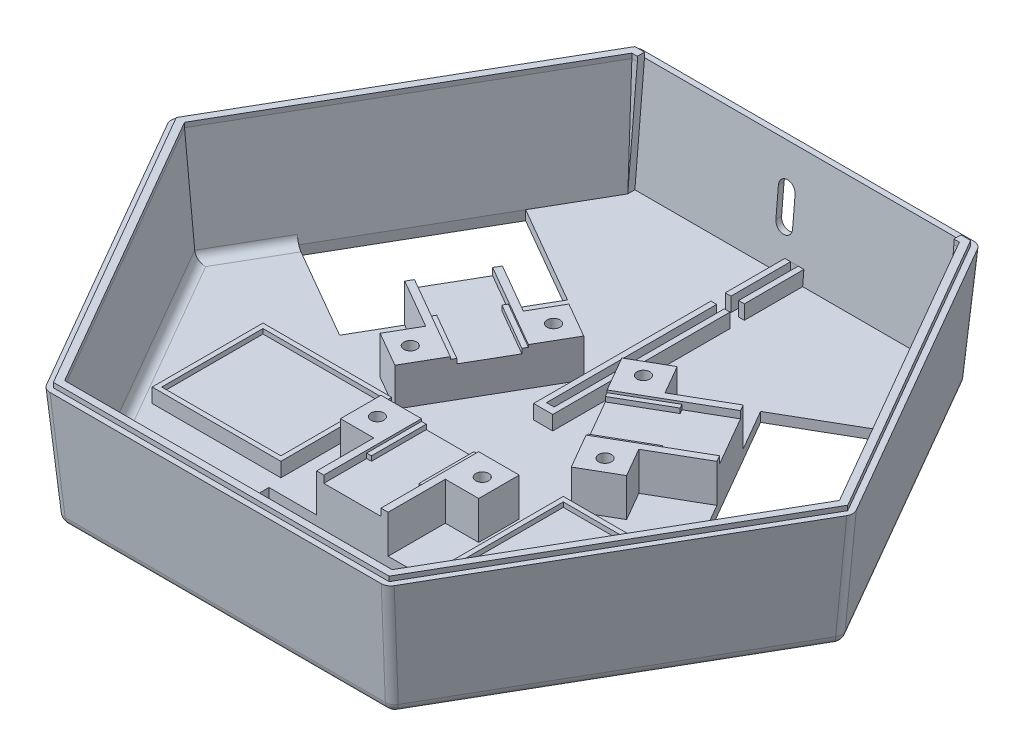
SolidWorks part; units mm, degrees
ref_plane "Front Plane" through (0, 0, 0) normal (0, 0, 1) x (1, 0, 0)
ref_plane "Top Plane" through (0, 0, 0) normal (0, 1, 0) x (1, 0, 0)
ref_plane "Right Plane" through (0, 0, 0) normal (1, 0, 0) x (0, 0, -1)
sketch "Sketch1" plane through (0, 0, 0) normal (0, 1, 0) x (1, 0, 0)
  line L1 (69.282, 0) -> (34.641, 60)
  line L2 (34.641, 60) -> (-34.641, 60)
  line L3 (-34.641, 60) -> (-69.282, 0)
  line L4 (-69.282, 0) -> (-34.641, -60)
  line L5 (-34.641, -60) -> (34.641, -60)
  line L6 (34.641, -60) -> (69.282, 0)
  circle A0 centre (0, 0) radius 60 construction
extrude "Boss-Extrude1" add sketch "Sketch1" along normal blind 25 draft 5 draft outward yes
sketch "Sketch2" plane through (0, 25, 0) normal (0, 1, 0) x (1, 0, 0)
  line L1 (68.7047, 0) -> (34.3523, 59.5)
  line L2 (34.3523, 59.5) -> (-34.3523, 59.5)
  line L3 (-34.3523, 59.5) -> (-68.7047, 0)
  line L4 (-68.7047, 0) -> (-34.3523, -59.5)
  line L5 (-34.3523, -59.5) -> (34.3523, -59.5)
  line L6 (34.3523, -59.5) -> (68.7047, 0)
  circle A0 centre (0, 0) radius 59.5 construction
extrude "Cut-Extrude1" cut sketch "Sketch2" against normal blind 23 draft 5
sketch "Sketch4" plane through (0, 2, 0) normal (0, 1, 0) x (1, 0, 0)
  line L0 (-33.1906, -57.4878) -> (33.1906, -57.4878) construction
  line L1 (-17.5, -57.4878) -> (17.5, -57.4878)
  line L2 (-17.5, -57.4878) -> (-17.5, -33.4878)
  line L3 (-17.5, -33.4878) -> (17.5, -33.4878)
  line L4 (17.5, -57.4878) -> (17.5, -33.4878)
  line L5 (-41.0359, 43.8993) -> (-20.2513, 31.8993)
  line L6 (-41.0359, 43.8993) -> (-58.5359, 13.5884)
  line L7 (-58.5359, 13.5884) -> (-37.7513, 1.5884)
  line L8 (-20.2513, 31.8993) -> (-37.7513, 1.5884)
  line L9 (58.5359, 13.5884) -> (37.7513, 1.5884)
  line L10 (58.5359, 13.5884) -> (41.0359, 43.8993)
  line L11 (41.0359, 43.8993) -> (20.2513, 31.8993)
  line L12 (37.7513, 1.5884) -> (20.2513, 31.8993)
  point P6 (0, -57.4878)
  point P7 (0, -57.4878)
  point P19 (0, 0)
  dimension "D1" = 24
  dimension "D2" = 35
  dimension "D3" = 0
  dimension "D4" = 0
  dimension "D5" = 3
extrude "Cut-Extrude3" cut sketch "Sketch4" against normal blind 3
ref_plane "Plane1" through (0, 0, -50) normal (0, 0, 1) x (1, 0, 0)
sketch "Sketch20" plane through (0, 0, -50) normal (0, 0, 1) x (1, 0, 0)
  line L0 (-2.625, 16.65) -> (-2.625, 10.65) construction
  line L1 (-0.875, 16.65) -> (-0.875, 10.65)
  line L2 (-4.375, 16.65) -> (-4.375, 10.65)
  line L3 (-17.5, 2) -> (17.5, 2) construction
  arc A0 (-0.875, 16.65) -> (-4.375, 16.65) centre (-2.625, 16.65) ccw
  arc A1 (-4.375, 10.65) -> (-0.875, 10.65) centre (-2.625, 10.65) ccw
  point P2 (-2.625, 13.65)
  point P7 (-2.625, 8.9)
  point P8 (-2.625, 18.4)
  point P9 (-4.375, 13.65)
  point P10 (-0.875, 13.65)
  dimension "D1" = 9.5
  dimension "D2" = 3.5
  dimension "D3" = 6.9
extrude "Cut-Extrude12" cut sketch "Sketch20" against normal blind 17
sketch "Sketch21" plane through (0, 2, 0) normal (0, 1, 0) x (1, 0, 0)
  line L1 (-45, -7.2378) -> (-18, -7.2378)
  line L2 (-45, -7.2378) -> (-45, -30.4878)
  line L3 (-45, -30.4878) -> (-18, -30.4878)
  line L4 (-18, -7.2378) -> (-18, -30.4878)
  line L5 (17.5, -33.4878) -> (-17.5, -33.4878) construction
  line L7 (18, -7.2378) -> (45, -7.2378)
  line L8 (18, -7.2378) -> (18, -30.4878)
  line L9 (18, -30.4878) -> (45, -30.4878)
  line L10 (45, -7.2378) -> (45, -30.4878)
  line L11 (17.5, -33.4878) -> (-17.5, -33.4878) construction
  dimension "D1" = 27
  dimension "D2" = 23.25
  dimension "D4" = 3
  dimension "D6" = 27
  dimension "D7" = 3
extrude "Boss-Extrude7" add sketch "Sketch21" along normal blind 3
sketch "Sketch22" plane through (0, 5, 0) normal (0, 1, 0) x (1, 0, 0)
  line L0 (-18, -30.4878) -> (-18, -7.2378) construction
  line L1 (-44, -8.2378) -> (-19, -8.2378)
  line L2 (-44, -8.2378) -> (-44, -29.4878)
  line L3 (-44, -29.4878) -> (-19, -29.4878)
  line L4 (-19, -8.2378) -> (-19, -29.4878)
  line L5 (19, -8.2378) -> (44, -8.2378)
  line L6 (19, -8.2378) -> (19, -29.4878)
  line L7 (19, -29.4878) -> (44, -29.4878)
  line L8 (44, -8.2378) -> (44, -29.4878)
  line L9 (-45, -7.2378) -> (-45, -30.4878) construction
  line L10 (-45, -30.4878) -> (-18, -30.4878) construction
  line L11 (-18, -7.2378) -> (-45, -7.2378) construction
  line L12 (45, -7.2378) -> (18, -7.2378) construction
  line L13 (18, -7.2378) -> (18, -30.4878) construction
  dimension "D1" = 1
  dimension "D2" = 1
  dimension "D3" = 1
  dimension "D4" = 1
  dimension "D5" = 25
  dimension "D6" = 21.25
  dimension "D7" = 1
  dimension "D8" = 1
extrude "Cut-Extrude13" cut sketch "Sketch22" against normal blind 1
fillet "Fillet2" radius 2 6 edges at (25.3453, 2, 57.4878) (-25.3453, 2, 57.4878) (-62.4585, 2, -6.7942) (-49.7859, 2, 28.7439) (49.7859, 2, 28.7439) (62.4585, 2, -6.7942)
fillet "Fillet3" radius 2 12 edges at (-51.9615, 0, -30) (-35.2724, 12.5, -61.0936) (0, 0, -60) (35.2724, 12.5, -61.0936) (51.9615, 0, -30) (70.5448, 12.5, 0) (51.9615, 0, 30) (35.2724, 12.5, 61.0936) (0, 0, 60) (-51.9615, 0, 30) (-35.2724, 12.5, 61.0936) (-70.5448, 12.5, 0)
sketch "Sketch24" plane through (0, 25, 0) normal (0, 1, 0) x (1, 0, 0)
  line L1 (70.4367, 0) -> (35.2184, 61)
  line L2 (35.2184, 61) -> (-35.2184, 61)
  line L3 (-35.2184, 61) -> (-70.4367, 0)
  line L4 (-70.4367, 0) -> (-35.2184, -61)
  line L5 (-35.2184, -61) -> (35.2184, -61)
  line L6 (35.2184, -61) -> (70.4367, 0)
  circle A0 centre (0, 0) radius 61 construction
extrude "Boss-Extrude8" add sketch "Sketch24" along normal blind 1
sketch "Sketch25" plane through (0, 26, 0) normal (0, 1, 0) x (1, 0, 0)
  line L1 (68.7047, 0) -> (34.3523, 59.5)
  line L2 (34.3523, 59.5) -> (-34.3523, 59.5)
  line L3 (-34.3523, 59.5) -> (-68.7047, 0)
  line L4 (-68.7047, 0) -> (-34.3523, -59.5)
  line L5 (-34.3523, -59.5) -> (34.3523, -59.5)
  line L6 (34.3523, -59.5) -> (68.7047, 0)
  circle A0 centre (0, 0) radius 59.5 construction
extrude "Cut-Extrude16" cut sketch "Sketch25" against normal blind 1
sketch "Sketch26" plane through (0, 2, 0) normal (0, 1, 0) x (1, 0, 0)
  line L0 (-25.2513, 23.2391) -> (-14.8589, 17.2391)
  line L1 (-37.7513, 1.5884) -> (-20.2513, 31.8993) construction
  line L2 (-14.8589, 17.2391) -> (-11.3589, 23.3012)
  line L3 (-11.3589, 23.3012) -> (-3.9977, 19.0512)
  line L4 (-3.9977, 19.0512) -> (-18.4977, -6.0635)
  line L5 (-18.4977, -6.0635) -> (-25.8589, -1.8135)
  line L6 (-25.8589, -1.8135) -> (-22.3589, 4.2487)
  line L7 (-22.3589, 4.2487) -> (-32.7513, 10.2487)
  line L8 (-32.7513, 10.2487) -> (-25.2513, 23.2391)
  line L9 (25.2513, 23.2391) -> (32.7513, 10.2487)
  line L10 (32.7513, 10.2487) -> (22.3589, 4.2487)
  line L11 (22.3589, 4.2487) -> (25.8589, -1.8135)
  line L12 (25.8589, -1.8135) -> (18.4977, -6.0635)
  line L13 (18.4977, -6.0635) -> (3.9977, 19.0512)
  line L14 (3.9977, 19.0512) -> (11.3589, 23.3012)
  line L15 (11.3589, 23.3012) -> (14.8589, 17.2391)
  line L16 (14.8589, 17.2391) -> (25.2513, 23.2391)
  line L17 (7.5, -33.4878) -> (-7.5, -33.4878)
  line L18 (-7.5, -33.4878) -> (-7.5, -21.4878)
  line L19 (-7.5, -21.4878) -> (-14.5, -21.4878)
  line L20 (-14.5, -21.4878) -> (-14.5, -12.9878)
  line L21 (-14.5, -12.9878) -> (14.5, -12.9878)
  line L22 (14.5, -12.9878) -> (14.5, -21.4878)
  line L23 (14.5, -21.4878) -> (7.5, -21.4878)
  line L24 (7.5, -21.4878) -> (7.5, -33.4878)
  point P4 (-29.0013, 16.7439)
  point P11 (-29.0013, 16.7439)
  point P31 (0, 0)
  dimension "D1" = 15
  dimension "D2" = 12
  dimension "D3" = 12
  dimension "D4" = 7
  dimension "D5" = 7
  dimension "D6" = 8.5
  dimension "D7" = 8.5
  dimension "D8" = 0
  dimension "D9" = 3
extrude "Boss-Extrude9" add sketch "Sketch26" along normal blind 8 contours L8 L0 L2 L3 L4 L5 L6 L7 | L17 L18 L19 L20 L21 L22 L23 L24 | L9 L10 L11 L12 L13 L14 L15 L16
sketch "Sketch37" plane through (0, 0, 0) normal (1, 0, 0) x (0, 0, -1)
  line L0 (57.4878, 2) -> (58.9776, 2)
  line L1 (58.9776, 2) -> (61, 25)
  line L2 (61, 25) -> (61.3953, 29.4952)
  line L3 (61.3953, 29.4952) -> (58.5935, 29.7415)
  line L4 (58.5935, 29.7415) -> (55.5776, 2)
  line L5 (43.8993, 2) -> (57.4878, 2) construction
  line L6 (55.5776, 2) -> (57.4878, 2)
extrude "Cut-Extrude21" cut sketch "Sketch37" against normal blind 33.2 and the other way blind 33.2
sketch "Sketch38" plane through (0, 0, 0) normal (1, 0, 0) x (0, 0, -1)
  line L0 (58.9776, 2) -> (59.2414, 5)
  line L1 (58.9776, 2) -> (61, 25) construction
  line L2 (59.2414, 5) -> (46.7414, 5)
  line L3 (46.7414, 5) -> (46.7414, 2)
  line L4 (43.8993, 2) -> (57.4714, 2) construction
  line L5 (46.7414, 2) -> (58.9776, 2)
  line L6 (43.7414, 2) -> (43.7414, 5)
  line L7 (13.5884, 2) -> (43.8993, 2) construction
  line L8 (43.7414, 5) -> (6.5414, 5)
  line L9 (6.5414, 5) -> (6.5414, 2)
  line L10 (6.5414, 2) -> (43.7414, 2)
  dimension "D1" = 3
  dimension "D2" = 12.5
  dimension "D3" = 3
  dimension "D4" = 37.2
extrude "Boss-Extrude10" add sketch "Sketch38" along normal blind 2 and the other way blind 2
sketch "Sketch40" plane through (0, 5, 0) normal (0, 1, 0) x (1, 0, 0)
  line L3 (-2, 59.2414) -> (2, 59.2414) construction
  line L4 (-0.805, 59.2414) -> (0.805, 59.2414)
  line L6 (-0.805, 59.2414) -> (-0.805, 8.0414)
  line L7 (-0.805, 8.0414) -> (0.805, 8.0414)
  line L8 (0.805, 8.0414) -> (0.805, 59.2414)
  line L9 (-2, 6.5414) -> (2, 6.5414) construction
  point P5 (0, 6.5414)
  dimension "D1" = 1.5
  dimension "D2" = 1.195
  dimension "D3" = 1.61
extrude "Cut-Extrude23" cut sketch "Sketch40" against normal blind 3
sketch "Sketch44" plane through (0, 10, 0) normal (0, 1, 0) x (1, 0, 0)
  line L0 (7.5, -33.4878) -> (-7.5, -33.4878) construction
  line L1 (-6, -33.4878) -> (6, -33.4878)
  line L2 (-6, -33.4878) -> (-6, -12.9878)
  line L3 (-6, -12.9878) -> (6, -12.9878)
  line L4 (6, -33.4878) -> (6, -12.9878)
  line L5 (-14.5, -12.9878) -> (14.5, -12.9878) construction
  line L6 (-26.0013, 21.94) -> (-8.2477, 11.69)
  line L7 (-26.0013, 21.94) -> (-32.0013, 11.5477)
  line L8 (-32.0013, 11.5477) -> (-14.2477, 1.2977)
  line L9 (-8.2477, 11.69) -> (-14.2477, 1.2977)
  line L10 (32.0013, 11.5477) -> (14.2477, 1.2977)
  line L11 (32.0013, 11.5477) -> (26.0013, 21.94)
  line L12 (26.0013, 21.94) -> (8.2477, 11.69)
  line L13 (14.2477, 1.2977) -> (8.2477, 11.69)
  point P20 (0, 0)
  dimension "D1" = 12
  dimension "D2" = 1.5
  dimension "D3" = 3
extrude "Cut-Extrude24" cut sketch "Sketch44" against normal blind 1.5
sketch "Sketch46" plane through (0, 8.5, 0) normal (0, 1, 0) x (1, 0, 0)
  line L1 (-6, -12.9878) -> (-5, -12.9878)
  line L2 (-6, -12.9878) -> (-6, -24.4878)
  line L3 (-6, -24.4878) -> (-5, -24.4878)
  line L4 (-5, -12.9878) -> (-5, -24.4878)
  line L5 (6, -12.9878) -> (5, -12.9878)
  line L6 (6, -12.9878) -> (6, -24.4878)
  line L7 (6, -24.4878) -> (5, -24.4878)
  line L8 (5, -12.9878) -> (5, -24.4878)
extrude "Boss-Extrude11" add sketch "Sketch46" along normal blind 1
sketch "Sketch47" plane through (0, 8.5, 0) normal (0, 1, 0) x (1, 0, 0)
  line L0 (-14.2477, 1.2977) -> (-13.7477, 2.1638)
  line L1 (-14.2477, 1.2977) -> (-8.2477, 11.69) construction
  line L2 (-13.7477, 2.1638) -> (-23.707, 7.9138)
  line L3 (-23.707, 7.9138) -> (-24.207, 7.0477)
  line L4 (-32.0013, 11.5477) -> (-14.2477, 1.2977) construction
  line L5 (-24.207, 7.0477) -> (-14.2477, 1.2977)
  line L6 (-8.2477, 11.69) -> (-8.7477, 10.824)
  line L7 (-8.7477, 10.824) -> (-18.707, 16.574)
  line L8 (-18.707, 16.574) -> (-18.207, 17.44)
  line L9 (-8.2477, 11.69) -> (-26.0013, 21.94) construction
  line L10 (-18.207, 17.44) -> (-8.2477, 11.69)
  point P16 (0, 0)
extrude "Boss-Extrude12" add sketch "Sketch47" along normal blind 1
sketch "Sketch48" plane through (0, 8.5, 0) normal (0, 1, 0) x (1, 0, 0)
  line L0 (14.2477, 1.2977) -> (13.7477, 2.1638)
  line L1 (8.2477, 11.69) -> (14.2477, 1.2977) construction
  line L2 (13.7477, 2.1638) -> (23.707, 7.9138)
  line L3 (23.707, 7.9138) -> (24.207, 7.0477)
  line L4 (14.2477, 1.2977) -> (32.0013, 11.5477) construction
  line L5 (24.207, 7.0477) -> (14.2477, 1.2977)
  line L6 (8.2477, 11.69) -> (8.7477, 10.824)
  line L7 (18.4977, -6.0635) -> (3.9977, 19.0512) construction
  line L8 (8.7477, 10.824) -> (18.707, 16.574)
  line L9 (18.707, 16.574) -> (18.207, 17.44)
  line L10 (26.0013, 21.94) -> (8.2477, 11.69) construction
  line L11 (18.207, 17.44) -> (8.2477, 11.69)
extrude "Boss-Extrude13" add sketch "Sketch48" along normal blind 1
sketch "Sketch49" plane through (0, 10, 0) normal (0, 1, 0) x (1, 0, 0)
  line L0 (-18.4977, -6.0635) -> (-25.8589, -1.8135) construction
  line L1 (-25.8589, -1.8135) -> (-22.3589, 4.2487) construction
  line L2 (-14.8589, 17.2391) -> (-11.3589, 23.3012) construction
  line L3 (-11.3589, 23.3012) -> (-3.9977, 19.0512) construction
  line L4 (3.9977, 19.0512) -> (11.3589, 23.3012) construction
  line L6 (8.2477, 11.69) -> (3.9977, 19.0512) construction
  line L7 (22.3589, 4.2487) -> (25.8589, -1.8135) construction
  line L8 (25.8589, -1.8135) -> (18.4977, -6.0635) construction
  line L9 (6, -12.9878) -> (14.5, -12.9878) construction
  line L12 (14.5, -12.9878) -> (14.5, -21.4878) construction
  line L13 (-14.5, -21.4878) -> (-14.5, -12.9878) construction
  line L14 (-14.5, -12.9878) -> (-6, -12.9878) construction
  circle A0 centre (-20.4283, -0.9074) radius 1.35
  circle A1 centre (-9.4283, 18.1452) radius 1.35
  circle A2 centre (9.4283, 18.1452) radius 1.35
  circle A3 centre (20.4283, -0.9074) radius 1.35
  circle A4 centre (11, -17.2378) radius 1.35
  circle A5 centre (-11, -17.2378) radius 1.35
  point P34 (0, 0)
  point P36 (-11.4095, -17.4025)
  dimension "D1" = 3.5
  dimension "D3" = 4.25
  dimension "D5" = 3.5
  dimension "D7" = 4.25
  dimension "D9" = 4.25
  dimension "D13" = 2.7
  dimension "D14" = 2.7
  dimension "D15" = 2.7
  dimension "D16" = 2.7
  dimension "D17" = 2.7
  dimension "D18" = 2.7
  dimension "D2" = 4.25
  dimension "D4" = 3.5
  dimension "D6" = 4.25
  dimension "D8" = 3.5
  dimension "D10" = 3.5
  dimension "D11" = 3.5
  dimension "D12" = 4.25
extrude "Cut-Extrude25" cut sketch "Sketch49" against normal blind 6
